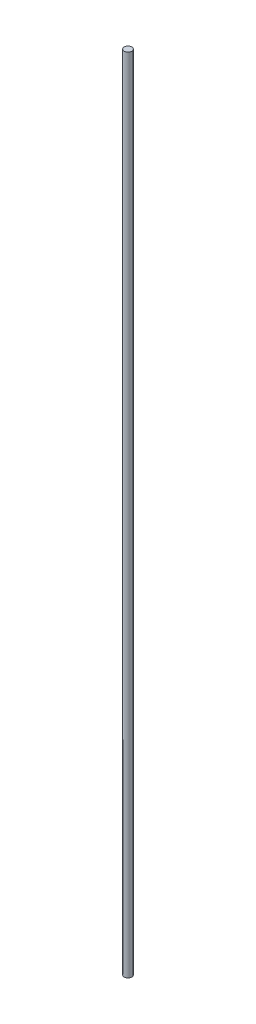
SolidWorks part; units mm, degrees
ref_plane "Спереди" through (0, 0, 0) normal (0, 0, 1) x (1, 0, 0)
ref_plane "Сверху" through (0, 0, 0) normal (0, 1, 0) x (1, 0, 0)
ref_plane "Справа" through (0, 0, 0) normal (1, 0, 0) x (0, 0, -1)
sketch "Эскиз2" plane through (0, 0, 0) normal (0, 0, 1) x (1, 0, 0)
  line L0 (2.5, 352.5571) -> (-7.5, 352.5571) construction
  line L5 (-2.5, 352.5571) -> (0, 352.5571)
  line L6 (-2.5, 352.5571) -> (-2.5, -176.8429)
  line L7 (-2.5, -176.8429) -> (0, -176.8429)
  line L8 (0, 352.5571) -> (0, -176.8429)
  line L9 (-2.5, 352.5571) -> (0, -176.8429) construction
  line L10 (-2.5, -176.8429) -> (0, 352.5571) construction
  line L13 (-260.5047, -176.8429) -> (37.4953, -176.8429) construction
  point P0 (-1.25, 87.8571)
  point P12 (0, 0)
  dimension "D1" = 2.5
revolve "Повернуть1" add sketch "Эскиз2" angle 360 about L6
equation "\"Ширина груза\"= 160"
equation "\"Глубина груза\"= 240"
equation "\"Высота груза\"= 160"
equation "\"Ширина ячейки\"= \"Ширина груза\" + 10"
equation "\"Глубина ячейки\"= \"Глубина груза\" + 10"
equation "\"Высота ячейки\"= \"Высота груза\" + 10 + 13"
equation "\"Колво ячеек ширина\"= 2"
equation "\"Колво ячеек высота\"= 2"
equation "\"Толщина стенки\" = \"Толщина тонких панелей\""
equation "\"Крепление дверцы\"= 5 "
equation "\"Ширина рейки\"= \"Толщина шестерни\""
equation "\"Высота рейки\"= 20"
equation "\"Высота пола\" = 2*\"Толщина тонких панелей\""
equation "\"Колво полозьев\"= 5"
equation "\"Отступ рейки\"= 20"
equation "\"Глубина каретки\"= \"Глубина ячейки\" + 30 + \"Мотор Y высота корпуса\" + 20 + \"Удлинение платформы по глубине\""
equation "\"Длинна рейки\" = (\"Ширина ячейки\"+\"Толщина вертикальных стенок\"+\"Крепление дверцы\")*\"Колво ячеек ширина\"+\"Ширина ячейки выгрузки\"*\"Колво выгрузки\"+\"Толщина вертикальных стенок\"+2*\"Отступ крепления мотора фиксации\"-\"Крепление дверцы\"*\"Колво ячеек ширина\""
equation "\"Отступ шпильки\"= 26"
equation "\"Диаметр шпильки\"= 5"
equation "\"Длинна шпильки\" = (\"Высота ячейки\"+\"Толщина горизонтальных плит\"+\"Высота пола\")*\"Колво ячеек высота\"+2*(\"Толщина горизонтальных плит\"+\"Отступ рейки\")"
equation "\"D1@Эскиз2\"= \"Диаметр шпильки\" / 2"
equation "\"Ширина пластины\" = 50"
equation "\"Высота зона выгрузки\"= \"Высота ячейки\" * 2 + \"Толщина стенки\" * 2"
equation "\"Колво выгрузки\"= 1"
equation "\"Отступ крепления мотора фиксации\" = (70-\"Толщина вертикальных стенок\")/2"
equation "\"Мотор X ширина корпуса\"= 42.3"
equation "\"Мотор X высота корпуса\"= 42.3"
equation "\"Мотор X длина корпуса\"= 40"
equation "\"Мотор X вылет вала\"= 19.8"
equation "\"Мотор Y ширина корпуса\"= 42.3"
equation "\"Мотор Y высота корпуса\"= 42.3"
equation "\"Мотор Y длина корпуса\"= 48"
equation "\"Мотор Y вылет вала\"= 30"
equation "\"Мотор Z ширина корпуса\"= 42"
equation "\"Мотор Z высота корпуса\"= 42"
equation "\"Мотор Z длина корпуса\"= 40"
equation "\"Мотор Z вылет вала\"= 23"
equation "\"Мотор диаметр вала ПРЕДВ\"= 5"
equation "\"Мотор шаг крепления ПРЕДВ\"= 31"
equation "\"Мотор диаметр отверстий ПРЕДВ\"= 3"
equation "\"Мотор глубина отверстий ПРЕДВ\"= 4.5"
equation "\"Мотор диаметр буртика ПРЕДВ\"= 22"
equation "\"Мотор высота буртика ПРЕДВ\"= 2"
equation "\"Мотор диаметр шкива ПРЕДВ\"= 16"
equation "\"Мотор длина шкива ПРЕДВ\"= 12"
equation "\"Мотор отступ шкива ПРЕДВ\"= 5"
equation "\"Мотор X шаг градусов\"= 1.8"
equation "\"Мотор X ток А\"= 1.5"
equation "\"Мотор X сопротивление Ом\"= 1.3"
equation "\"Мотор X индуктивность мГн\"= 2"
equation "\"Мотор Y шаг градусов\"= 1.8"
equation "\"Мотор Y ток А\"= 2.2"
equation "\"Мотор Y сопротивление Ом\"= 0.9"
equation "\"Мотор Y индуктивность мГн\"= 2"
equation "\"Мотор Z шаг градусов\"= 1.8"
equation "\"Мотор Z ток А\"= 1"
equation "\"Мотор Z сопротивление Ом\"= 4"
equation "\"Мотор Z индуктивность мГн\"= 8"
equation "\"Мотор Y диаметр ротора\"= 25.78"
equation "\"Ширина ячейки выгрузки\" = \"Ширина ячейки\"+\"Толщина вертикальных стенок\"+2*\"Отступ крепления мотора фиксации\""
equation "\"Толщина тонких панелей\" = 6"
equation "\"Толщина вертикальных стенок\" = 6"
equation "\"Толщина горизонтальных плит\" = 6"
equation "\"Базовая высота корпуса\"= (\"Высота ячейки\"+\"Толщина тонких панелей\"+\"Высота пола\")*\"Колво ячеек высота\"+6*\"Толщина тонких панелей\"+\"Мотор X ширина корпуса\"+\"Мотор Y ширина корпуса\"+75"
equation "\"Высота корпуса\"= (\"Высота ячейки\"+\"Толщина горизонтальных плит\"+\"Высота пола\")*\"Колво ячеек высота\"+2*\"Толщина горизонтальных плит\"+4*\"Толщина тонких панелей\"+\"Мотор X ширина корпуса\"+\"Мотор Y ширина корпуса\"+75"
equation "\"Смещение центра корпуса\"= (\"Высота корпуса\"-\"Базовая высота корпуса\")/2-(\"Толщина горизонтальных плит\"-\"Толщина тонких панелей\")"
equation "\"Отметка пола\"= -\"Базовая высота корпуса\"/2+\"Толщина тонких панелей\""
equation "\"Отметка потолка\"= \"Отметка пола\"+\"Высота корпуса\"-2*\"Толщина горизонтальных плит\""
equation "\"Отметка верхней полки\"= \"Отметка потолка\"-(28+\"Толщина тонких панелей\")-\"Высота ячейки\"-\"Высота пола\""
equation "\"Отметка нижней полки\"= \"Отметка верхней полки\"-\"Высота ячейки\"-\"Высота пола\"-\"Толщина горизонтальных плит\""
equation "\"Толщина шестерни\"= 10"
